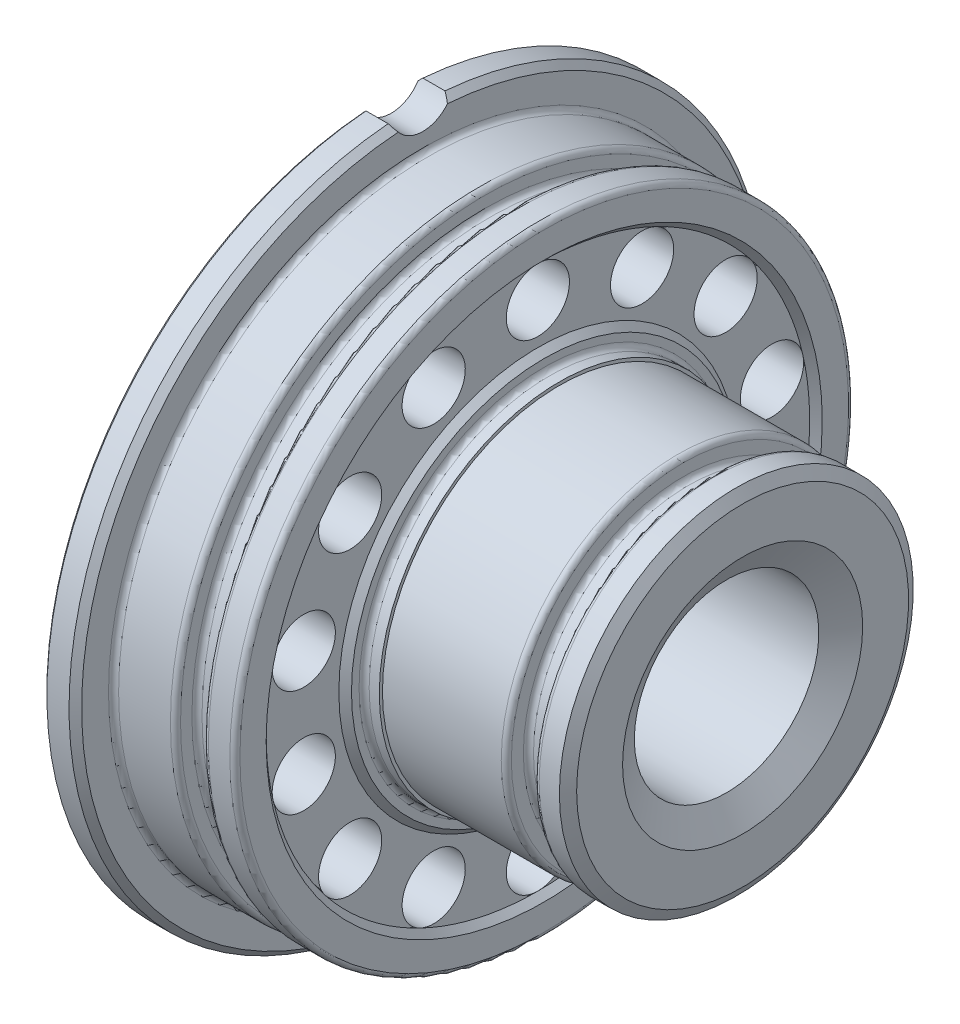
SolidWorks part; units mm, degrees
material "EN36A"
ref_plane "Front Plane" through (0, 0, 0) normal (0, 0, 1) x (1, 0, 0)
ref_plane "Top Plane" through (0, 0, 0) normal (0, 1, 0) x (1, 0, 0)
ref_plane "Right Plane" through (0, 0, 0) normal (1, 0, 0) x (0, 0, -1)
sketch "Sketch1" plane through (0, 0, 0) normal (0, 0, 1) x (1, 0, 0)
  line L0 (0, 0) -> (33.2077, 0) construction
  line L1 (0.4, 7.3) -> (26.5298, 7.3)
  line L2 (0.4, 7.3) -> (0.4, 13.5)
  line L4 (0, 13.9) -> (0, 27.25)
  line L5 (0.25, 27.5) -> (2, 27.5)
  line L6 (2.5, 27) -> (2.5, 24.875)
  line L7 (2.9, 24.475) -> (7, 24.475)
  line L8 (7.4, 24.075) -> (7.4, 23.175)
  line L9 (7.8, 22.775) -> (9.2, 22.775)
  line L10 (9.6, 23.175) -> (9.6, 24.075)
  line L11 (10, 24.475) -> (11.7, 24.475)
  line L12 (12.1, 24.075) -> (12.1, 22)
  line L13 (13.3, 14) -> (22.7, 14)
  line L14 (23.1, 12.65) -> (23.1, 13.6)
  line L15 (23.5, 12.25) -> (24.9, 12.25)
  line L16 (25.3, 12.65) -> (25.3, 13.6)
  line L17 (25.7, 14) -> (27.3, 14)
  line L18 (27.8, 13.134) -> (27.8, 9.5)
  line L19 (0.4, 13.5) -> (0, 13.9)
  line L21 (12.1, 15.25) -> (12.1, 14.65)
  line L22 (12.1, 15.25) -> (11.6, 15.75)
  line L23 (11.6, 21.5) -> (11.6, 15.75)
  line L24 (12.1, 22) -> (11.6, 21.5)
  line L25 (2, 27.5) -> (2.5, 27)
  line L26 (0, 27.25) -> (0.25, 27.5)
  line L27 (27.8, 9.5) -> (26.5298, 7.3)
  line L28 (27.3, 14) -> (27.8, 13.134)
  line L29 (12.5, 14.25) -> (13.3, 14.25)
  line L30 (13.3, 14.25) -> (13.3, 14)
  arc A0 (12.1, 14.65) -> (12.5, 14.25) centre (12.5, 14.65) ccw
  arc A1 (7.4, 23.175) -> (7.8, 22.775) centre (7.8, 23.175) ccw
  arc A2 (9.2, 22.775) -> (9.6, 23.175) centre (9.2, 23.175) ccw
  arc A3 (23.1, 12.65) -> (23.5, 12.25) centre (23.5, 12.65) ccw
  arc A4 (24.9, 12.25) -> (25.3, 12.65) centre (24.9, 12.65) ccw
  arc A6 (2.5, 24.875) -> (2.9, 24.475) centre (2.9, 24.875) ccw
  arc A7 (11.7, 24.475) -> (12.1, 24.075) centre (11.7, 24.075) cw
  arc A8 (7, 24.475) -> (7.4, 24.075) centre (7, 24.075) cw
  arc A9 (9.6, 24.075) -> (10, 24.475) centre (10, 24.075) cw
  arc A10 (22.7, 14) -> (23.1, 13.6) centre (22.7, 13.6) cw
  arc A11 (25.3, 13.6) -> (25.7, 14) centre (25.7, 13.6) cw
  point P33 (7.4, 22.775)
  point P36 (9.6, 22.775)
  point P39 (23.1, 12.25)
  point P42 (25.3, 12.25)
  point P48 (12.1, 24.475)
  point P53 (9.6, 24.475)
  point P58 (25.3, 14)
  dimension "D28" = 30.5
  dimension "D30" = 0.4
  dimension "D31" = 45
  dimension "D32" = 0.4
  dimension "D17" = 0.4
  dimension "D36" = 0.4
  dimension "D37" = 0.4
  dimension "D1" = 14.6
  dimension "D2" = 27
  dimension "D3" = 0.4
  dimension "D4" = 45
  dimension "D5" = 55
  dimension "D6" = 0.25
  dimension "D7" = 48.95
  dimension "D8" = 2.2
  dimension "D9" = 2.2
  dimension "D10" = 12.1
  dimension "D11" = 45.55
  dimension "D12" = 2.5
  dimension "D13" = 28
  dimension "D14" = 0.5
  dimension "D15" = 44
  dimension "D16" = 28.5
  dimension "D18" = 24.5
  dimension "D19" = 2.5
  dimension "D20" = 27.8
  dimension "D22" = 45
  dimension "D23" = 2.5
  dimension "D24" = 60
  dimension "D25" = 0.5
  dimension "D26" = 19
  dimension "D27" = 30
  dimension "D29" = 45
  dimension "D33" = 45
  dimension "D34" = 14.5
  dimension "D35" = 0.5
revolve "Revolve1" add sketch "Sketch1" angle 360 about L0
sketch "Sketch2" plane through (0, 0, 0) normal (-1, 0, 0) x (0, 0, 1)
  line L0 (0, 0) -> (37.309, 0) construction
  line L1 (0, 0) -> (0, 29.0181) construction
  circle A0 centre (0, 19) radius 2.5
  circle A1 centre (0, -19) radius 2.5
  dimension "D1" = 5
  dimension "D2" = 38
extrude "Extrude1" cut sketch "Sketch2" against normal up to next
sketch "Sketch3" plane through (0, 0, 0) normal (-1, 0, 0) x (0, 0, 1)
  line L0 (0, 0) -> (0, 32.8515) construction
  circle A0 centre (0, 28.5) radius 2.5
  circle A2 centre (0, 0) radius 27.5 construction
  circle A4 centre (0, 0) radius 27.5 construction
  dimension "D2" = 5
  dimension "D1" = 28.5
extrude "Extrude2" cut sketch "Sketch3" against normal up to next
pattern_circular "CirPattern1" count 7 over 360 about axis through (0, 0, 0) along (-1, 0, 0) of "Extrude1"
